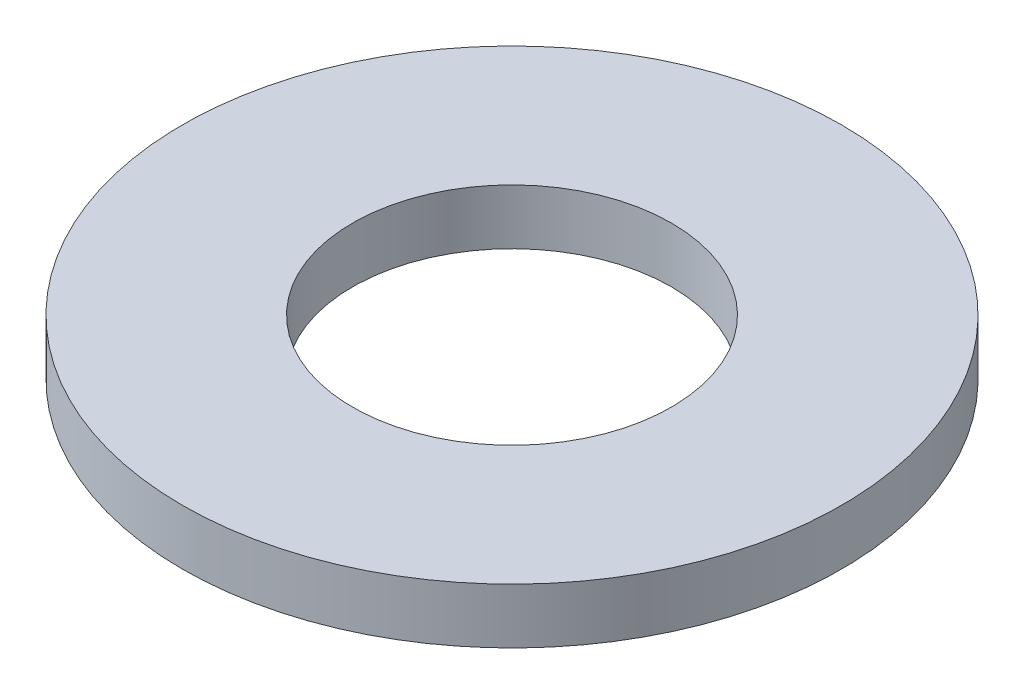
SolidWorks part; units mm, degrees
ref_plane "Front Plane" through (0, 0, 0) normal (0, 0, 1) x (1, 0, 0)
ref_plane "Top Plane" through (0, 0, 0) normal (0, 1, 0) x (1, 0, 0)
ref_plane "Right Plane" through (0, 0, 0) normal (1, 0, 0) x (0, 0, -1)
sketch "Sketch1" plane through (0, 0, 0) normal (0, 1, 0) x (1, 0, 0)
  circle A0 centre (0, 0) radius 77.5
  dimension "FLANGE_OD" = 155
extrude "Boss-Extrude1" add sketch "Sketch1" along normal blind 13
sketch "Sketch2" plane through (0, 0, 0) normal (0, 1, 0) x (1, 0, 0)
  circle A0 centre (0, 0) radius 37.5
  dimension "BORE_D" = 75
extrude "Cut-Extrude1" cut sketch "Sketch2" along normal through all
sketch "Sketch3" plane through (0, 13, 0) normal (0, 1, 0) x (1, 0, 0)
  circle A0 centre (0, 0) radius 23.866 construction
  circle A1 centre (-23.866, 0) radius 1.8784
  dimension "BOLT_D" = 3.7569
  dimension "BOLT_PCD" = 47.7321
extrude "Cut-Extrude2" cut sketch "Sketch3" against normal blind 8.5005 rebuild error yes
pattern_circular "CirPattern1" count 3 over 360 rebuild error yes
